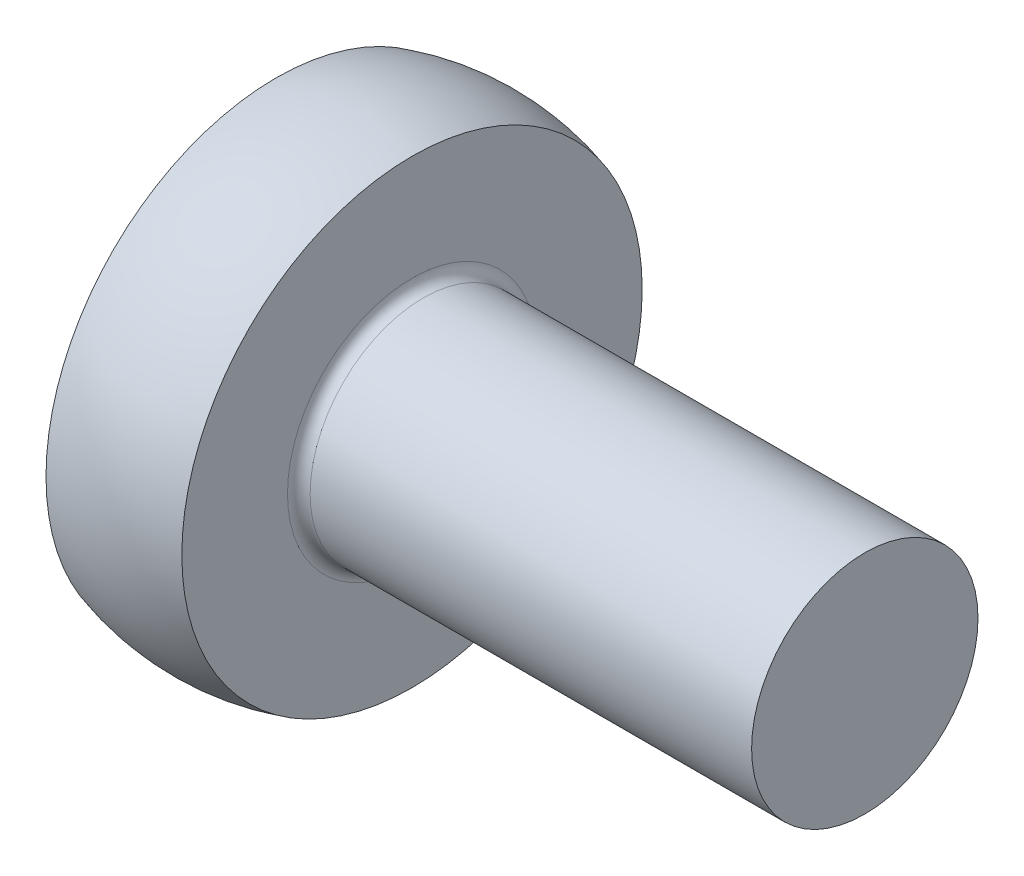
SolidWorks part; units mm, degrees
ref_plane "Front" through (0, 0, 0) normal (0, 0, 1) x (1, 0, 0)
ref_plane "Top" through (0, 0, 0) normal (0, 1, 0) x (1, 0, 0)
ref_plane "Right" through (0, 0, 0) normal (1, 0, 0) x (0, 0, -1)
sketch "Sketch1" plane through (0, 0, 0) normal (0, 0, 1) x (1, 0, 0)
  line L0 (0, 2.0333) -> (0, 0)
  line L1 (1.2, 2.0333) -> (1.2, 1)
  line L2 (0, 0) -> (5.2, 0)
  line L3 (5.2, 0) -> (5.2, 1)
  line L4 (5.2, 1) -> (1.2, 1)
  line L5 (-2.3183, 0) -> (6.9456, 0) construction
  arc A0 (1.2, 2.0333) -> (0, 2.0333) centre (0.6, 0) ccw
  dimension "D3" = 0.6
revolve "Base-Revolve" add sketch "Sketch1" angle 360 about L5
fillet "Fillet1" radius 0.1 1 edges at (1.2, 0, 1)
equation "\"D3@Sketch1\" = \"K@Sketch1\" / 2"
